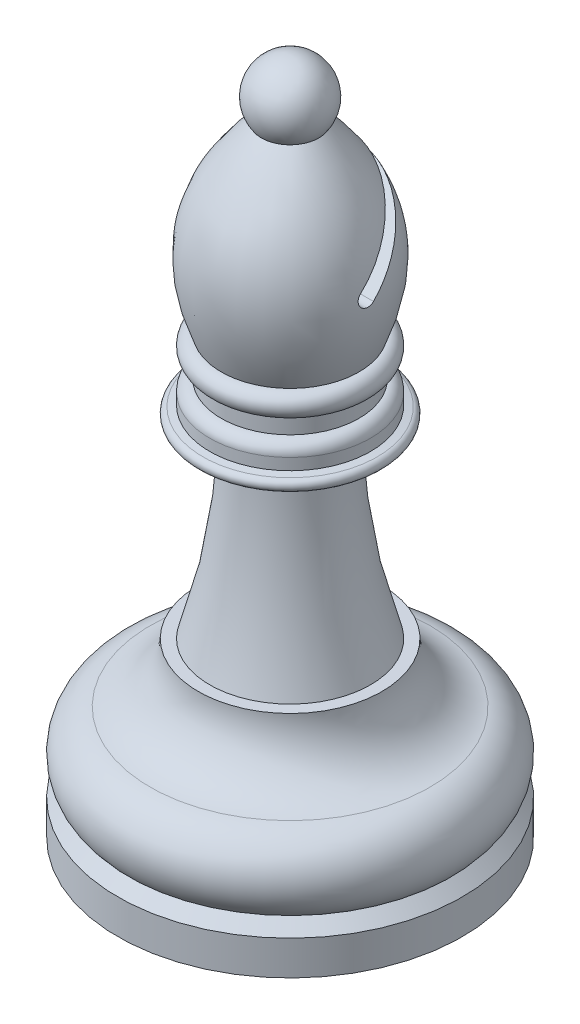
SolidWorks part; units mm, degrees
ref_plane "Front Plane" through (0, 0, 0) normal (0, 0, 1) x (1, 0, 0)
ref_plane "Top Plane" through (0, 0, 0) normal (0, 1, 0) x (1, 0, 0)
ref_plane "Right Plane" through (0, 0, 0) normal (1, 0, 0) x (0, 0, -1)
sketch "Sketch1" plane through (0, 0, 0) normal (1, 0, 0) x (0, 0, -1)
  line L0 (0, 0) -> (0, 59)
  line L1 (0, 0) -> (15, 0)
  line L2 (15, 0) -> (15, 3)
  line L3 (15, 3) -> (14, 4)
  line L4 (8, 15) -> (7, 15)
  line L5 (4.5, 31) -> (7.5811, 31.5066)
  line L6 (7.5902, 32.4918) -> (7, 32.6)
  line L7 (7, 32.6) -> (7, 33.6)
  line L8 (6, 34.6) -> (6, 36.1)
  arc A0 (14, 4) -> (12.1911, 9.8806) centre (11.5, 6.4495) ccw
  arc A1 (8, 15) -> (12.1911, 9.8806) centre (13.2222, 15) ccw
  arc A2 (4.5, 31) -> (7, 15) centre (56.95, 31) ccw
  arc A3 (7.5811, 31.5066) -> (7.5902, 32.4918) centre (7.5, 32) ccw
  arc A4 (7, 33.6) -> (6, 34.6) centre (6, 33.6) ccw
  arc A5 (6, 36.1) -> (6, 38.1) centre (6, 37.1) ccw
  arc A6 (2.5, 54) -> (0, 59) centre (0, 55.875) ccw
  spline S0 degree 3 poles (2.5, 54) (7.0454, 49.2294) (8.6095, 44.6134) (6, 38.1) knots 0 0 0 0 1 1 1 1
  point P9 (8, 15)
  point P11 (8, 32)
  point P12 (8, 15)
  point P15 (4.5, 31)
  point P17 (15, 6.4495)
  point P24 (2.5, 54)
  point P29 (7, 37.1)
  dimension "D6" = 7
  dimension "D14" = 1
  dimension "D18" = 2
  dimension "D1" = 59
  dimension "D2" = 15
  dimension "D3" = 3
  dimension "D4" = 45
  dimension "D5" = 1
  dimension "D7" = 15
  dimension "D8" = 8
  dimension "D9" = 1
  dimension "D10" = 4.5
  dimension "D11" = 31
  dimension "D12" = 7.5
  dimension "D13" = 32
  dimension "D15" = 7
  dimension "D16" = 0.6
  dimension "D17" = 1
  dimension "D19" = 1.5
  dimension "D20" = 54
  dimension "D21" = 2.5
revolve "Revolve1" add sketch "Sketch1" angle 360 about L0
sketch "Sketch2" plane through (0, 0, 0) normal (1, 0, 0) x (0, 0, -1)
  line L0 (5.1404, 51.2179) -> (-1.012, 45.0655)
  line L1 (5.1404, 51.2179) -> (6.1524, 50.2058)
  line L3 (6.1524, 50.2058) -> (0, 44.0534)
  line L4 (1.0253, 44.0534) -> (15.8283, 44.0534) construction
  arc A0 (-1.012, 45.0655) -> (0, 44.0534) centre (-0.506, 44.5594) ccw
  dimension "D1" = 45
extrude "Cut-Extrude1" cut sketch "Sketch2" against normal blind 10 and the other way blind 10
